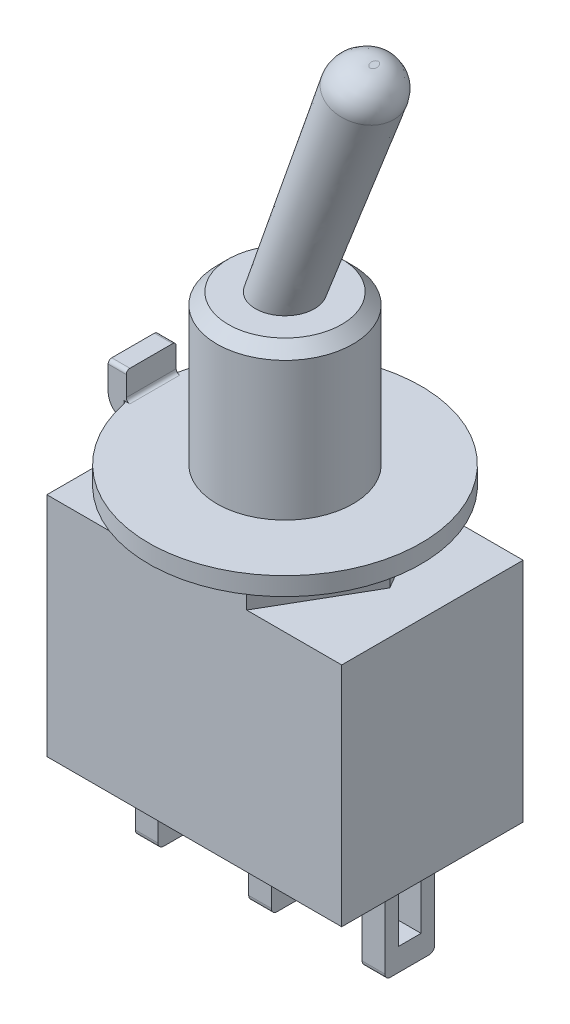
SolidWorks part; units mm, degrees
ref_plane "Спереди" through (0, 0, 0) normal (0, 0, 1) x (1, 0, 0)
ref_plane "Сверху" through (0, 0, 0) normal (0, 1, 0) x (1, 0, 0)
ref_plane "Справа" through (0, 0, 0) normal (1, 0, 0) x (0, 0, -1)
sketch "Эскиз1" plane through (0, 0, 0) normal (0, 1, 0) x (1, 0, 0)
  line L1 (-6.5, -4) -> (6.5, -4)
  line L2 (-6.5, -4) -> (-6.5, 4)
  line L3 (-6.5, 4) -> (6.5, 4)
  line L4 (6.5, -4) -> (6.5, 4)
  line L5 (-6.5, -4) -> (6.5, 4) construction
  line L6 (-6.5, 4) -> (6.5, -4) construction
  point P0 (0, 0)
  dimension "D1" = 8
  dimension "D2" = 13
extrude "Бобышка-Вытянуть1" add sketch "Эскиз1" along normal blind 10
sketch "Эскиз2" plane through (0, 0, 0) normal (0, -1, 0) x (1, 0, 0)
  line L0 (-0.5, -1.1) -> (-0.5, 1.1)
  line L1 (-5.5, -1.1) -> (-4.5, -1.1)
  line L2 (-5.5, -1.1) -> (-5.5, 1.1)
  line L3 (-5.5, 1.1) -> (-4.5, 1.1)
  line L4 (-4.5, -1.1) -> (-4.5, 1.1)
  line L5 (-5.5, -1.1) -> (-4.5, 1.1) construction
  line L6 (-5.5, 1.1) -> (-4.5, -1.1) construction
  line L7 (-0.5, -1.1) -> (0.5, -1.1)
  line L8 (0.5, -1.1) -> (0.5, 1.1)
  line L9 (-0.5, 1.1) -> (0.5, 1.1)
  line L10 (-0.5, 1.1) -> (0.5, -1.1) construction
  line L11 (-0.5, -1.1) -> (0.5, 1.1) construction
  line L12 (4.5, -1.1) -> (4.5, 1.1)
  line L13 (4.5, -1.1) -> (5.5, -1.1)
  line L14 (5.5, -1.1) -> (5.5, 1.1)
  line L15 (4.5, 1.1) -> (5.5, 1.1)
  line L16 (4.5, 1.1) -> (5.5, -1.1) construction
  line L17 (4.5, -1.1) -> (5.5, 1.1) construction
  line L18 (-5.5, -1.1) -> (-0.5, -1.1) construction
  point P0 (-5, 0)
  point P5 (0, 0)
  dimension "D1" = 2.2
  dimension "D2" = 1
  dimension "D4" = 5
  dimension "D3" = 3
extrude "Бобышка-Вытянуть2" add sketch "Эскиз2" along normal blind 4
fillet "Скругление1" radius 0.25 6 edges at (5, -4, -1.1) (0, -4, -1.1) (-5, -4, -1.1) (-5, -4, 1.1) (0, -4, 1.1) (5, -4, 1.1)
sketch "Эскиз3" plane through (5.5, 0, 0) normal (1, 0, 0) x (0, 0, -1)
  line L1 (0.5, -3) -> (-0.5, -3)
  line L2 (0.5, -3) -> (0.5, -1)
  line L3 (0.5, -1) -> (-0.5, -1)
  line L4 (-0.5, -3) -> (-0.5, -1)
  line L5 (0.5, -3) -> (-0.5, -1) construction
  line L6 (0.5, -1) -> (-0.5, -3) construction
  line L7 (0.85, -4) -> (-0.85, -4) construction
  point P0 (0, -2)
  point P5 (0, 0)
  dimension "D1" = 1
  dimension "D2" = 2
  dimension "D3" = 1
extrude "Вырез-Вытянуть1" cut sketch "Эскиз3" against normal through all both and the other way through all
sketch "Эскиз4" plane through (0, 10, 0) normal (0, 1, 0) x (1, 0, 0)
  circle A0 centre (0, 0) radius 3
extrude "Бобышка-Вытянуть3" add sketch "Эскиз4" along normal blind 9
sketch "Эскиз5" plane through (0, 10, 0) normal (0, 1, 0) x (1, 0, 0)
  line L1 (-4.6188, 0) -> (-2.3094, -4)
  line L2 (-2.3094, -4) -> (2.3094, -4)
  line L3 (2.3094, -4) -> (4.6188, 0)
  line L4 (4.6188, 0) -> (2.3094, 4)
  line L5 (2.3094, 4) -> (-2.3094, 4)
  line L6 (-2.3094, 4) -> (-4.6188, 0)
  circle A0 centre (0, 0) radius 3
  circle A1 centre (0, 0) radius 4 construction
  point P3 (-5.607, -0.538)
  point P11 (0, 0)
  dimension "D1" = 8
  dimension "D2" = 6
extrude "Бобышка-Вытянуть4" add sketch "Эскиз5" along normal blind 1.6
chamfer "Фаска1" distance 0.5 angle 45 1 edges at (0, 19, 3)
sketch "Эскиз6" plane through (0, 11.6, 0) normal (0, 1, 0) x (1, 0, 0)
  line L1 (-5.8983, 1.1) -> (-6.6983, 1.1)
  line L3 (-5.8983, -1.1) -> (-6.6983, -1.1)
  line L4 (-6.6983, 1.1) -> (-6.6983, -1.1)
  line L5 (-5.8983, 1.1) -> (-6.6983, -1.1) construction
  line L6 (-5.8983, -1.1) -> (-6.6983, 1.1) construction
  circle A0 centre (0, 0) radius 3
  arc A1 (-5.8983, -1.1) -> (-5.8983, 1.1) centre (0, 0) ccw
  point P4 (-6.2983, 0)
  point P9 (0, 0)
  point P10 (0, 0)
  dimension "D1" = 12
  dimension "D2" = 6
  dimension "D3" = 0.8
  dimension "D4" = 2.2
extrude "Бобышка-Вытянуть5" add sketch "Эскиз6" along normal blind 0.8 contours A1 L1 L4 L3
sketch "Эскиз7" plane through (0, 12.4, 0) normal (0, 1, 0) x (1, 0, 0)
  line L1 (-6.6983, -1.1) -> (-5.8983, -1.1)
  line L2 (-6.6983, -1.1) -> (-6.6983, 1.1)
  line L3 (-6.6983, 1.1) -> (-5.8983, 1.1)
  line L4 (-5.8983, -1.1) -> (-5.8983, 1.1)
extrude "Бобышка-Вытянуть6" add sketch "Эскиз7" along normal blind 1.2
fillet "Скругление2" radius 0.8 1 edges at (-6.6983, 11.6, 0)
fillet "Скругление3" radius 0.16 2 edges at (-5.8983, 12, 1.1) (-5.8983, 12, -1.1)
fillet "Скругление4" radius 0.16 3 edges at (-5.8983, 12.4, 0) (-6.2983, 13.6, 1.1) (-6.2983, 13.6, -1.1)
sketch "Эскиз8" plane through (0, 19, 0) normal (0, 1, 0) x (1, 0, 0)
  circle A0 centre (0, 0) radius 1.3
ref_plane "Плоскость1" through (0, 30, 0) normal (0, 1, 0) x (1, 0, 0)
sketch "Эскиз9" plane through (0, 30, 0) normal (0, 1, 0) x (1, 0, 0)
  circle A0 centre (4, 0.1374) radius 1.5
  dimension "D1" = 4
loft "По сечениям1" add profiles "Эскиз9", "Эскиз8"
sketch "Эскиз10" plane through (0, 0, 0) normal (0, 0, 1) x (1, 0, 0)
  line L0 (0, 19) -> (4, 30) construction
  line L1 (2.5, 19) -> (-2.5, 19) construction
  line L2 (5.5, 30) -> (2.5, 30) construction
  point P7 (2.5, 30)
ref_plane "Плоскость2" through (2.5, 30, 0) normal (0.3417, 0.9398, 0) x (0.9398, -0.3417, 0)
sketch "Эскиз12" plane through (2.5, 30, 0) normal (0.3417, 0.9398, 0) x (0.9398, -0.3417, 0)
  line L1 (-0.6512, 2.2539) -> (4.0186, 2.2539)
  line L2 (-0.6512, 2.2539) -> (-0.6512, -2.1363)
  line L3 (-0.6512, -2.1363) -> (4.0186, -2.1363)
  line L4 (4.0186, 2.2539) -> (4.0186, -2.1363)
extrude "Вырез-Вытянуть2" cut sketch "Эскиз12" along normal through all
fillet "Скругление5" radius 1.25 1 edges at (5.125, 29.0455, 0.0484)
